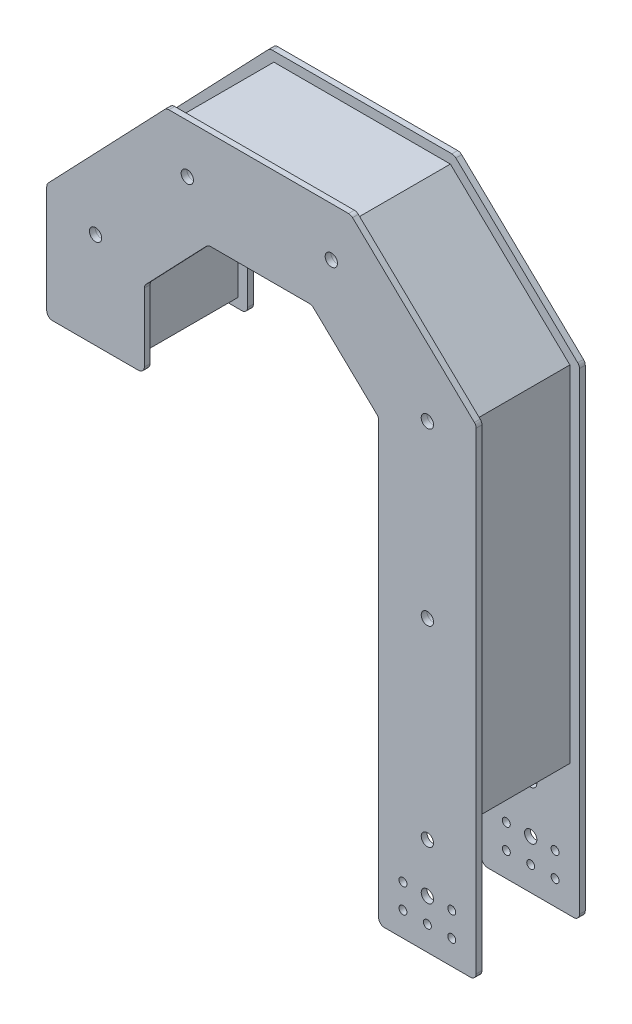
SolidWorks part; units mm, degrees
ref_plane "Front Plane" through (0, 0, 0) normal (0, 0, 1) x (1, 0, 0)
ref_plane "Top Plane" through (0, 0, 0) normal (0, 1, 0) x (1, 0, 0)
ref_plane "Right Plane" through (0, 0, 0) normal (1, 0, 0) x (0, 0, -1)
sketch "Sketch1" plane through (0, 0, 0) normal (0, 0, 1) x (1, 0, 0)
  line L0 (0, 0) -> (0, 188.6623) construction
  line L1 (0, 188.6623) -> (-50, 236.43) construction
  line L2 (-50, 236.43) -> (-125, 236.43) construction
  line L3 (-125, 236.43) -> (-172.7677, 186.43) construction
  line L4 (-172.7677, 186.43) -> (-172.7677, 136.43) construction
  line L5 (25.4, 0) -> (25.4, 199.5246)
  line L6 (25.4, 199.5246) -> (-39.8171, 261.83)
  line L7 (-39.8171, 261.83) -> (-135.8623, 261.83)
  line L8 (-135.8623, 261.83) -> (-198.1677, 196.613)
  line L9 (-198.1677, 196.613) -> (-198.1677, 136.43)
  line L10 (-25.4, 0) -> (-25.4, 177.8)
  line L11 (-25.4, 177.8) -> (-60.1829, 211.03)
  line L12 (-60.1829, 211.03) -> (-114.1377, 211.03)
  line L13 (-114.1377, 211.03) -> (-147.3677, 176.2471)
  line L14 (-147.3677, 176.2471) -> (-147.3677, 136.43)
  line L15 (-25.4, 0) -> (-25.4, -50.8)
  line L16 (-25.4, -50.8) -> (25.4, -50.8)
  line L17 (25.4, -50.8) -> (25.4, 0)
  line L18 (-25.4, 0) -> (25.4, 0) construction
  line L19 (-198.1677, 136.43) -> (-147.3677, 136.43)
  line L20 (54.736, 199.5246) -> (54.736, 0) construction
  line L21 (0, 0) -> (0, -50.8) construction
  line L22 (0, -50.8) -> (-25.4, -25.4) construction
  line L23 (-25.4, -25.4) -> (0, -25.4) construction
  circle A0 centre (-172.7677, 186.43) radius 3.2
  circle A1 centre (-125, 236.43) radius 3.2
  circle A2 centre (-50, 236.43) radius 3.2
  circle A3 centre (0, 188.6623) radius 3.2
  circle A4 centre (0, 0) radius 3.2
  circle A5 centre (0, 99.7623) radius 3.2
  circle A6 centre (0, -25.4) radius 3.2
  circle A7 centre (-12.7, -25.4) radius 2.07
  circle A8 centre (12.7, -25.4) radius 2.07
  circle A9 centre (-12.7, -38.1) radius 2.07
  circle A10 centre (12.7, -38.1) radius 2.07
  circle A11 centre (0, -38.1) radius 2.07
  point P31 (54.736, 99.7623)
  point P34 (0, -50.8)
  point P46 (0, 0)
  dimension "D9" = 6.4
  dimension "D10" = 6.4
  dimension "D11" = 4.14
  dimension "D1" = 177.8
  dimension "D2" = 50
  dimension "D3" = 75
  dimension "D4" = 50
  dimension "D5" = 226.308
  dimension "D8" = 50.8
  dimension "D6" = 25.4
  dimension "D7" = 25.4
extrude "Boss-Extrude1" add sketch "Sketch1" along normal mid plane 3
sketch "Sketch2" plane through (0, 0, 1.5) normal (0, 0, 1) x (1, 0, 0)
  line L12 (-20.4, 17.7) -> (20.4, 17.7)
  line L24 (20.4, -45.8) -> (20.4, 197.3864)
  line L25 (20.4, 197.3864) -> (-41.8216, 256.83)
  line L26 (-41.8216, 256.83) -> (-133.7241, 256.83)
  line L27 (-133.7241, 256.83) -> (-193.1677, 194.6084)
  line L28 (-193.1677, 194.6084) -> (-193.1677, 141.43)
  line L29 (-193.1677, 141.43) -> (-152.3677, 141.43)
  line L30 (-152.3677, 141.43) -> (-152.3677, 178.2516)
  line L31 (-152.3677, 178.2516) -> (-116.2759, 216.03)
  line L32 (-116.2759, 216.03) -> (-58.1784, 216.03)
  line L33 (-58.1784, 216.03) -> (-20.4, 179.9383)
  line L34 (-20.4, 179.9383) -> (-20.4, -45.8)
  line L35 (-20.4, -45.8) -> (20.4, -45.8)
  line L36 (20.4, -45.8) -> (20.4, 197.3864)
  line L37 (20.4, 197.3864) -> (-41.8216, 256.83)
  line L38 (-41.8216, 256.83) -> (-133.7241, 256.83)
  line L39 (-133.7241, 256.83) -> (-193.1677, 194.6084)
  line L40 (-193.1677, 194.6084) -> (-193.1677, 141.43)
  line L41 (-193.1677, 141.43) -> (-152.3677, 141.43)
  line L42 (-152.3677, 141.43) -> (-152.3677, 178.2516)
  line L43 (-152.3677, 178.2516) -> (-116.2759, 216.03)
  line L44 (-116.2759, 216.03) -> (-58.1784, 216.03)
  line L45 (-58.1784, 216.03) -> (-20.4, 179.9383)
  line L46 (-20.4, 179.9383) -> (-20.4, -45.8)
  line L47 (-20.4, -45.8) -> (20.4, -45.8)
  circle M17 centre (-50, 236.43) radius 3.2
  circle M18 centre (-172.7677, 186.43) radius 3.2
  circle M31 centre (-125, 236.43) radius 3.2
  circle M32 centre (0, 188.6623) radius 3.2
  circle M33 centre (0, 99.7623) radius 3.2
  dimension "D2" = 63.5
  dimension "D1" = 5
extrude "Boss-Extrude2" add sketch "Sketch2" along normal blind 50.8 separate body contours L45 L46 L12 L36 L37 L38 L39 L40 L41 L42 L43 L44 M17 M32 M33 M31 M18 region at (-17.1938, 98.8191, 1.5)
extrude "Boss-Extrude4" add sketch "Sketch1<3>" along normal blind 3 from surface separate body starting at face at (-46.8, 236.43, 52.3)
sketch "Sketch1<3>" plane through (0, 0, 0) normal (0, 0, 1) x (1, 0, 0) same geometry as "Sketch1"
fillet "Fillet1" radius 3 12 edges at (25.4, -50.8, 0) (-25.4, -50.8, 0) (-25.4, 177.8, 0) (-60.1829, 211.03, 0) (-198.1677, 196.613, 0) (-135.8623, 261.83, 0) (-39.8171, 261.83, 0) (25.4, 199.5246, 0) (-147.3677, 176.2471, 0) (-114.1377, 211.03, 0) (-198.1677, 136.43, 0) (-147.3677, 136.43, 0)
fillet "Fillet2" radius 3 12 edges at (-147.3677, 136.43, 53.8) (-198.1677, 196.613, 53.8) (-135.8623, 261.83, 53.8) (-39.8171, 261.83, 53.8) (25.4, 199.5246, 53.8) (25.4, -50.8, 53.8) (-25.4, -50.8, 53.8) (-25.4, 177.8, 53.8) (-60.1829, 211.03, 53.8) (-114.1377, 211.03, 53.8) (-147.3677, 176.2471, 53.8) (-198.1677, 136.43, 53.8)
